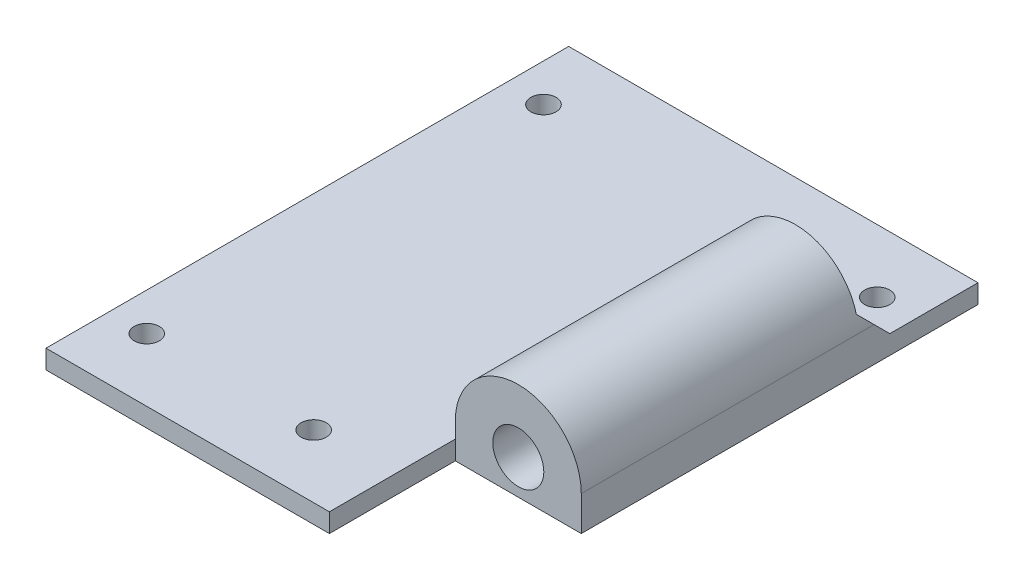
SolidWorks part; units mm, degrees
ref_plane "Front Plane" through (0, 0, 0) normal (0, 0, 1) x (1, 0, 0)
ref_plane "Top Plane" through (0, 0, 0) normal (0, 1, 0) x (1, 0, 0)
ref_plane "Right Plane" through (0, 0, 0) normal (1, 0, 0) x (0, 0, -1)
sketch "Sketch1" plane through (0, 0, 0) normal (0, 1, 0) x (1, 0, 0)
  line L0 (45, -83) -> (45, -63)
  line L1 (0, 0) -> (65, 0)
  line L2 (0, 0) -> (0, -83)
  line L3 (0, -83) -> (45, -83)
  line L4 (65, 0) -> (65, -63)
  line L5 (45, -63) -> (65, -63)
  dimension "D1" = 65
  dimension "D2" = 83
  dimension "D3" = 20
  dimension "D4" = 45
extrude "Boss-Extrude1" add sketch "Sketch1" along normal blind 3
sketch "Sketch3" plane through (0, 3, 0) normal (0, 1, 0) x (1, 0, 0)
  line L0 (0, -10) -> (65, -10) construction
  line L1 (0, 0) -> (0, -83) construction
  line L2 (65, -63) -> (65, 0) construction
  line L3 (0, -73) -> (45, -73) construction
  line L4 (0, 0) -> (0, -83) construction
  line L5 (45, -83) -> (45, -63) construction
  circle A0 centre (6, -10) radius 2
  circle A1 centre (59, -10) radius 2
  circle A2 centre (6, -73) radius 2
  circle A3 centre (32.5, -73) radius 2
  dimension "D1" = 4
  dimension "D2" = 6
  dimension "D3" = 6
  dimension "D4" = 6
  dimension "D5" = 26.5
extrude "Cut-Extrude1" cut sketch "Sketch3" against normal blind 5
sketch "Sketch4" plane through (0, 0, 63) normal (0, 0, 1) x (1, 0, 0)
  line L0 (45, 3) -> (45, 5.5)
  line L1 (65, 5.5) -> (65, 3)
  line L2 (45, 3) -> (65, 3) construction
  line L3 (45, 3) -> (65, 3)
  line L9 (45, 3) -> (45, 0)
  line L10 (45, 0) -> (65, 0)
  line L13 (65, 0) -> (65, 3)
  line L14 (65, 3) -> (45, 3)
  line L15 (45, 3) -> (45, 0)
  line L16 (45, 0) -> (65, 0)
  line L19 (65, 0) -> (65, 3)
  arc A0 (45, 5.5) -> (65, 5.5) centre (55, 5.5) cw
  line M13 (65, 3) -> (45, 3)
  dimension "D1" = 10
  dimension "D2" = 5.5
  dimension "D3" = 0
extrude "Boss-Extrude4" add sketch "Sketch4" against normal blind 44 contours A0 L0 L1 M13 region at (55, 8.4176, 63)
sketch "Sketch6" plane through (0, 0, 63) normal (0, 0, 1) x (1, 0, 0)
  circle A0 centre (55, 5.5) radius 4.05
  dimension "D1" = 8.1
extrude "Cut-Extrude3" cut sketch "Sketch6" against normal blind 40
chamfer "Chamfer2" distance 5 angle 45 1 edges at (55, 3, 19)
